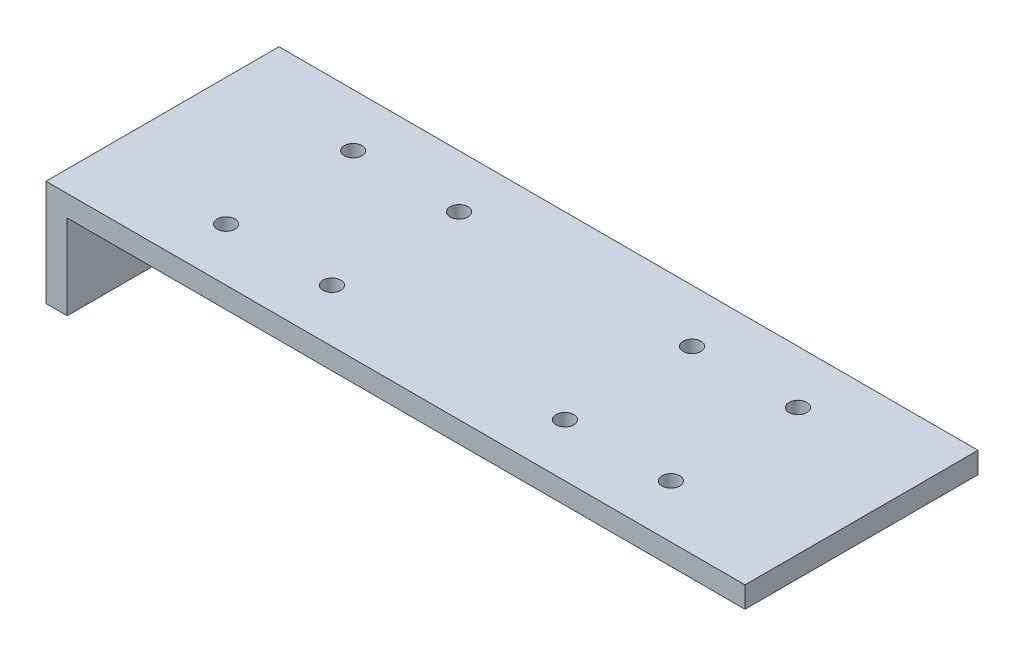
SolidWorks part; units mm, degrees
ref_plane "Front" through (0, 0, 0) normal (0, 0, 1) x (1, 0, 0)
ref_plane "Top" through (0, 0, 0) normal (0, 1, 0) x (1, 0, 0)
ref_plane "Right" through (0, 0, 0) normal (1, 0, 0) x (0, 0, -1)
sketch "草图1" plane through (0, 0, 0) normal (0, 1, 0) x (1, 0, 0)
  line L1 (-42.5, -27.5) -> (42.5, -27.5)
  line L2 (-42.5, -27.5) -> (-42.5, 27.5)
  line L3 (-42.5, 27.5) -> (42.5, 27.5)
  line L4 (42.5, -27.5) -> (42.5, 27.5)
  line L5 (-42.5, -27.5) -> (42.5, 27.5) construction
  line L6 (-42.5, 27.5) -> (42.5, -27.5) construction
  point P0 (0, 0)
extrude "凸台-拉伸1" add sketch "草图1" along normal blind 5
sketch "草图2" plane through (0, 0, 0) normal (0, -1, 0) x (1, 0, 0)
  line L0 (-42.5, 27.5) -> (42.5, 27.5) construction
  line L1 (-42.5, -27.5) -> (-37.5, -27.5)
  line L2 (-42.5, -27.5) -> (-42.5, 27.5)
  line L3 (-42.5, 27.5) -> (-37.5, 27.5)
  line L4 (-37.5, -27.5) -> (-37.5, 27.5)
  line L5 (-40, 27.5) -> (-40, -27.5) construction
  line L6 (-42.5, 0) -> (-37.5, 0) construction
  point P96 (-40, 0)
extrude "凸台-拉伸2" add sketch "草图2" along normal blind 20 contours L4 L3 L2 L1
sketch "草图3" plane through (42.5, 0, 0) normal (1, 0, 0) x (0, 0, -1)
  line L0 (-27.5, 0) -> (27.5, 0) construction
  line L1 (-27.5, 5) -> (27.5, 5)
  line L2 (-27.5, 5) -> (-27.5, 0)
  line L3 (-27.5, 0) -> (27.5, 0)
  line L4 (27.5, 5) -> (27.5, 0)
  line L5 (0, 0) -> (0, 5) construction
  line L6 (-27.5, 2.5) -> (27.5, 2.5) construction
  line L7 (27.5, 0) -> (-27.5, 0) construction
  point P88 (0, 2.5)
extrude "凸台-拉伸3" add sketch "草图3" along normal blind 80
sketch "草图5" plane through (0, 0, 0) normal (0, 0, 1) x (1, 0, 0)
  line L0 (-37.5, -20) -> (57.5, -20)
  line L7 (57.5, -20) -> (117.5, -20) construction
  line L8 (117.5, -20) -> (117.5, -80) construction
  line L9 (117.5, -80) -> (57.5, -20)
  dimension "D1" = 95
sketch "草图7" plane through (0, 5, 0) normal (0, 1, 0) x (1, 0, 0)
  line L0 (-42.5, 27.5) -> (-42.5, 15) construction
  line L1 (-42.5, 27.5) -> (-42.5, -27.5) construction
  line L2 (-42.5, 15) -> (-12.5, 15) construction
  line L3 (-12.5, 15) -> (12.5, 15) construction
  line L4 (122.5, 15) -> (92.5, 15) construction
  line L5 (122.5, 27.5) -> (122.5, -27.5) construction
  line L6 (92.5, 15) -> (67.5, 15) construction
  line L7 (0, 0) -> (12.5, 0) construction
  circle A0 centre (-12.5, 15) radius 2.1
  circle A1 centre (12.5, 15) radius 2.1
  circle A2 centre (67.5, 15) radius 2.1
  circle A3 centre (92.5, 15) radius 2.1
  circle A4 centre (92.5, -15) radius 2.1
  circle A5 centre (67.5, -15) radius 2.1
  circle A6 centre (12.5, -15) radius 2.1
  circle A7 centre (-12.5, -15) radius 2.1
extrude "切除-拉伸1" cut sketch "草图7" against normal blind 5
